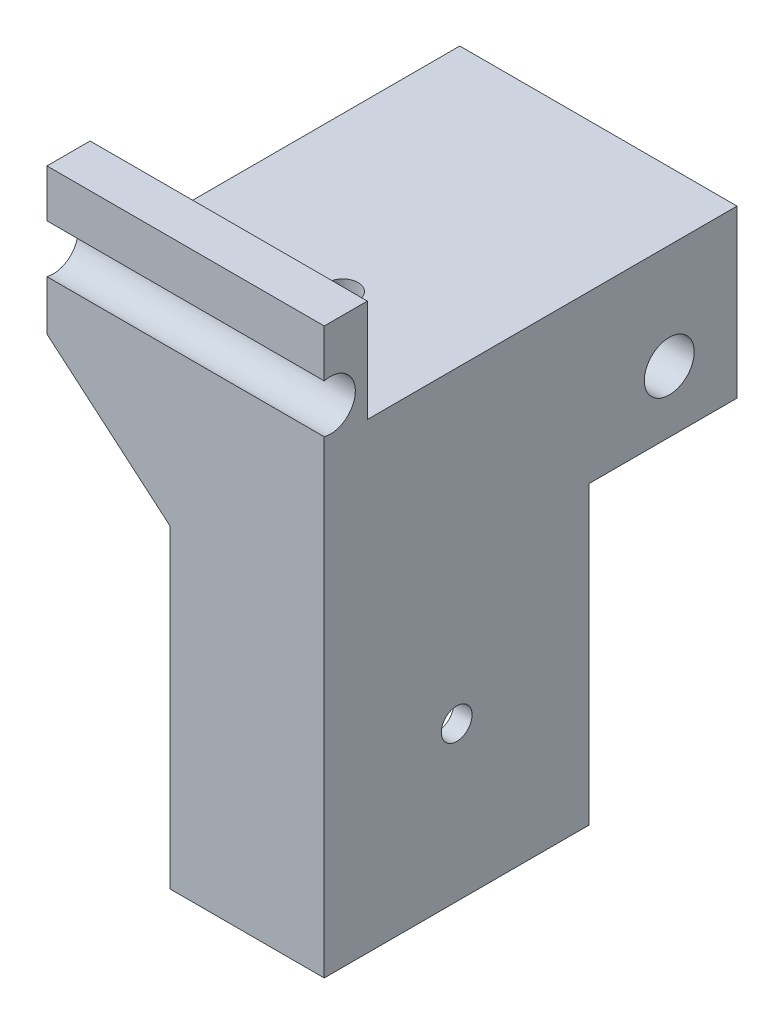
SolidWorks part; units mm, degrees
ref_plane "Front Plane" through (0, 0, 0) normal (0, 0, 1) x (1, 0, 0)
ref_plane "Top Plane" through (0, 0, 0) normal (0, 1, 0) x (1, 0, 0)
ref_plane "Right Plane" through (0, 0, 0) normal (1, 0, 0) x (0, 0, -1)
sketch "Sketch1" plane through (0, 0, 0) normal (0, 1, 0) x (1, 0, 0)
  line L0 (0, 0) -> (0, 40)
  line L1 (0, 40) -> (3, 40)
  line L2 (3, 40) -> (3, -3)
  line L3 (3, -3) -> (-22, -3)
  line L4 (-22, -3) -> (-22, 0)
  line L5 (-22, 0) -> (0, 0)
  dimension "D1" = 22
  dimension "D2" = 40
  dimension "D3" = 3
  dimension "D4" = 3
extrude "Boss-Extrude1" add sketch "Sketch1" along normal blind 75
sketch "Sketch2" plane through (0, 75, 0) normal (0, 1, 0) x (1, 0, 0)
  line L1 (0, 0) -> (-42, 0)
  line L2 (0, 0) -> (0, 40)
  line L3 (0, 40) -> (-42, 40)
  line L4 (-42, 0) -> (-42, 40)
  circle A0 centre (-17, 20) radius 2.5
  dimension "D3" = 5
  dimension "D1" = 42
  dimension "D2" = 17
extrude "Boss-Extrude2" add sketch "Sketch2" against normal blind 7
sketch "Sketch3" plane through (0, 0, 0) normal (0, 0, 1) x (1, 0, 0)
  line L0 (-22, 75) -> (-42, 75)
  line L1 (-42, 75) -> (-42, 68)
  line L2 (-42, 68) -> (-22, 51)
  line L3 (-22, 68) -> (-22, 0) construction
  line L4 (-22, 51) -> (-22, 75)
  dimension "D1" = 24
extrude "Boss-Extrude3" add sketch "Sketch3" along normal blind 3
sketch "Sketch4" plane through (3, 0, 0) normal (1, 0, 0) x (0, 0, -1)
  line L0 (-3, 75) -> (40, 75) construction
  circle A0 centre (18.5, 25) radius 2.5
  dimension "D1" = 5
  dimension "D2" = 50
extrude "Cut-Extrude1" cut sketch "Sketch4" against normal blind 3
sketch "Sketch5" plane through (-42, 0, 0) normal (-1, 0, 0) x (0, 0, 1)
  line L0 (-40, 75) -> (3, 75) construction
  line L1 (3, 75) -> (3, 76.0754)
  line L3 (2, 91.6487) -> (-4, 91.6487)
  line L4 (-4, 91.6487) -> (-4, 75)
  line L5 (-4, 75) -> (3, 75)
  line L6 (-40, 68) -> (0, 68) construction
  line L7 (3, 83.9246) -> (3, 91.6487)
  line L8 (3, 91.6487) -> (2, 91.6487)
  arc A0 (3, 83.9246) -> (3, 76.0754) centre (2, 80) ccw
  point P4 (-20, 68)
  line M1 (3, 75) -> (-40, 75)
  dimension "D1" = 8.1
  dimension "D2" = 22
  dimension "D3" = 6
  dimension "D4" = 12
extrude "Boss-Extrude4" add sketch "Sketch5" against normal up to surface (45 mm away) contours A0 L3 L4 M1 region at (-42, 84.6814, -1.0335) up to face at (3, 25, -21)
sketch "Sketch6" plane through (3, 0, 0) normal (1, 0, 0) x (0, 0, -1)
  line L0 (40, 75) -> (64, 75)
  line L1 (64, 75) -> (64, 48)
  line L2 (64, 48) -> (40, 48)
  line L3 (40, 75) -> (40, 0) construction
  line L4 (40, 48) -> (40, 75)
  line L5 (0, 68) -> (40, 68) construction
  circle A0 centre (53, 58) radius 4.05
  arc A1 (-3, 76.0754) -> (-3, 83.9246) centre (-2, 80) ccw construction
  point P5 (2.05, 80)
  dimension "D1" = 8.1
  dimension "D2" = 55
  dimension "D3" = 22
  dimension "D4" = 24
  dimension "D5" = 20
extrude "Boss-Extrude5" add sketch "Sketch6" against normal up to surface (45 mm away) up to face at (-42, 77.4775, -9.0056)
